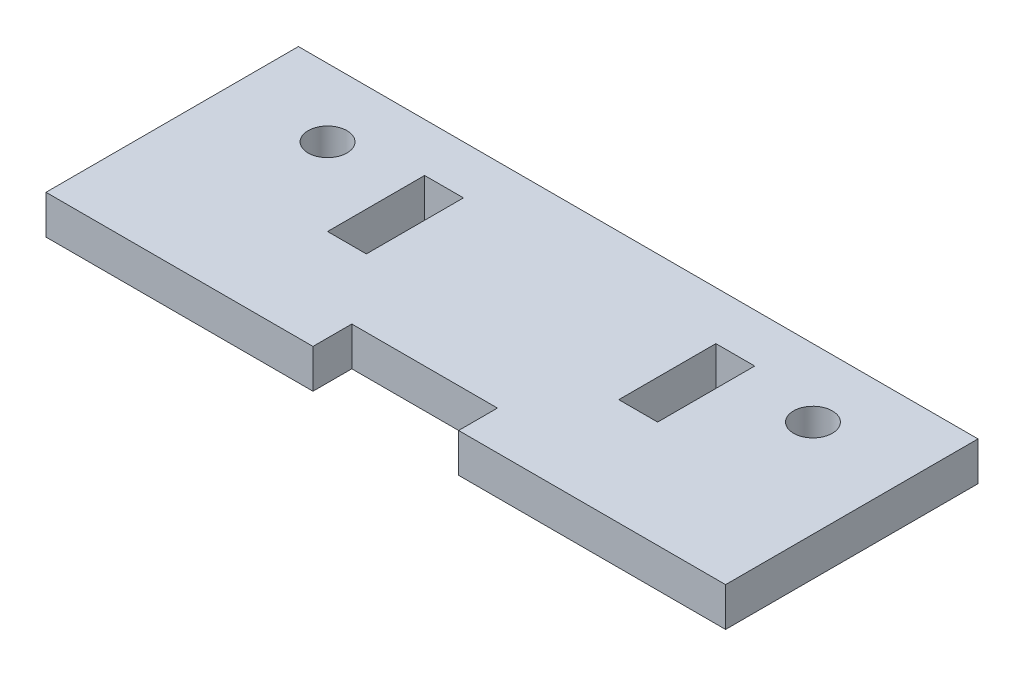
SolidWorks part; units mm, degrees
ref_plane "Front Plane" through (0, 0, 0) normal (0, 0, 1) x (1, 0, 0)
ref_plane "Top Plane" through (0, 0, 0) normal (0, 1, 0) x (1, 0, 0)
ref_plane "Right Plane" through (0, 0, 0) normal (1, 0, 0) x (0, 0, -1)
sketch "Sketch1" plane through (0, 0, 0) normal (0, 1, 0) x (1, 0, 0)
  line L0 (20, 26) -> (20, 0) construction
  line L1 (0, 0) -> (20, 0)
  line L2 (0, 0) -> (0, 26)
  line L3 (0, 26) -> (70, 26)
  line L4 (70, 0) -> (70, 26)
  line L5 (50, 26) -> (50, 0) construction
  line L6 (35, 26) -> (35, 4) construction
  line L7 (18, 21) -> (22, 21)
  line L8 (18, 21) -> (18, 11)
  line L9 (18, 11) -> (22, 11)
  line L10 (22, 21) -> (22, 11)
  line L11 (52, 11) -> (48, 11)
  line L12 (48, 21) -> (48, 11)
  line L13 (52, 21) -> (52, 11)
  line L14 (52, 21) -> (48, 21)
  line L15 (20, 0) -> (27.5, 0)
  line L17 (27.5, 0) -> (27.5, 26) construction
  line L26 (50, 0) -> (70, 0)
  line L27 (42.5, 0) -> (50, 0)
  line L30 (27.5, 0) -> (27.5, 4)
  line L31 (27.5, 4) -> (42.5, 4)
  line L32 (42.5, 0) -> (42.5, 4)
  circle A0 centre (10, 19) radius 2
  circle A2 centre (60, 19) radius 2
  dimension "D10" = 7.5
  dimension "D11" = 4
  dimension "D13" = 4
  dimension "D1" = 70
  dimension "D2" = 26
  dimension "D3" = 20
  dimension "D4" = 10
  dimension "D5" = 4
  dimension "D6" = 10
  dimension "D7" = 2
  dimension "D8" = 5
  dimension "D9" = 7
extrude "Boss-Extrude1" add sketch "Sketch1" along normal blind 4
